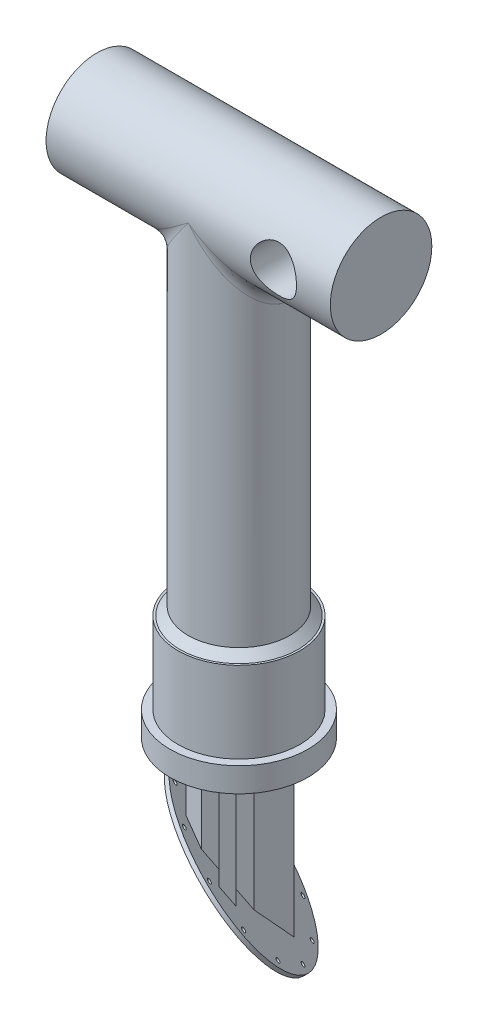
SolidWorks part; units mm, degrees
note: '?' marks a value the reader was unsure of.
ref_plane "前视基准面" through (0, 0, 0) normal (0, 0, 1) x (1, 0, 0)
ref_plane "上视基准面" through (0, 0, 0) normal (0, 1, 0) x (1, 0, 0)
ref_plane "右视基准面" through (0, 0, 0) normal (1, 0, 0) x (0, 0, -1)
sketch "草图1" plane through (0, 0, 0) normal (0, 1, 0) x (1, 0, 0)
  line L1 (0, 0) -> (1, 0)
  line L2 (0, 0) -> (0, 1)
  line L3 (0, 1) -> (1, 1)
  line L4 (1, 0) -> (1, 1)
  dimension "D1" = 1
  dimension "D2" = 1
ref_plane "基准面1" through (0, 1, 0) normal (0, 1, 0) x (1, 0, 0)
sketch "草图2" plane through (0, 1, 0) normal (0, 1, 0) x (1, 0, 0)
  line L1 (0, 0) -> (1, 0)
  line L2 (0, 0) -> (0, 1)
  line L3 (0, 1) -> (1, 1)
  line L4 (1, 0) -> (1, 1)
ref_axis "基准轴1" through (0, 0, 0) along (0.5774, 0.5774, -0.5774)?
ref_plane "基准面2" through (0, 0, 0) normal (0.5774, 0.5774, -0.5774) x (-0.8165, 0.4082, -0.4082)
sketch "草图3" plane through (0, 0, 0) normal (0.5774, 0.5774, -0.5774) x (-0.8165, 0.4082, -0.4082)
  circle A0 centre (0, 0) radius 112.5
  dimension "D1" = 225
extrude "凸台-拉伸1" add sketch "草图3" along normal blind 5 contours A0
sketch "草图5" plane through (0, 1, 0) normal (0, 1, 0) x (1, 0, 0)
  line L1 (0, 0) -> (-50, 0)
  line L2 (0, 0) -> (0, -50)
  line L3 (0, -50) -> (-50, -50)
  line L4 (-50, 0) -> (-50, -50)
  dimension "D1" = 50
  dimension "D2" = 50
ref_axis "基准轴2" through (-50, 1, 50) along (0, 1, 0)?
sketch "草图6" plane through (2.8868, 2.8868, -2.8868) normal (0.5774, 0.5774, -0.5774) x (-0.4082, -0.4082, -0.8165)
  line L0 (0, 0) -> (-51.6754, 89.5044) construction
  line L2 (-20.8207, 36.0624) -> (-102.3071, 177.201) construction
  circle A0 centre (-51.6754, 89.5044) radius 3
  dimension "D1" = 6
extrude "切除-拉伸1" cut sketch "草图6" against normal blind 5
pattern_circular "阵列(圆周)1" count 12 over 360 about axis through (0, 0, 0) along (0.5774, 0.5774, -0.5774) of "切除-拉伸1"
ref_plane "基准面3" through (0, 135, 0) normal (0, 1, 0) x (1, 0, 0)
sketch "草图7" [suppressed] plane through (0, 175, 0) normal (0, 1, 0) x (1, 0, 0)
  circle A0 centre (0, 0) radius 112.5
  dimension "D1" = 225
sketch "草图8" plane through (0, 135, 0) normal (0, 1, 0) x (1, 0, 0)
  line L0 (45.9279, 45.9279) -> (-45.9279, -45.9279) construction
  line L1 (-54.6804, -10.2893) -> (-10.2893, -54.6804)
  line L2 (-10.2893, -54.6804) -> (15.6559, -62.0463)
  line L3 (15.6559, -62.0463) -> (26.6929, -51.0092)
  line L4 (48.1974, -29.5048) -> (52.4911, 15.5798)
  line L5 (52.4911, 15.5798) -> (15.5798, 52.4911)
  line L6 (-54.6804, -10.2893) -> (-62.0463, 15.6559)
  line L7 (-62.0463, 15.6559) -> (-51.0092, 26.6929)
  line L8 (-29.5048, 48.1974) -> (15.5798, 52.4911)
  line L9 (26.6929, -51.0092) -> (45.0412, -69.3575)
  line L10 (45.0412, -69.3575) -> (55.2908, -59.1078)
  line L11 (55.2908, -59.1078) -> (36.9426, -40.7596)
  line L12 (36.9426, -40.7596) -> (48.1974, -29.5048)
  line L13 (-69.3575, 45.0412) -> (-59.1078, 55.2908)
  line L14 (-59.1078, 55.2908) -> (-40.7596, 36.9426)
  line L15 (-51.0092, 26.6929) -> (-69.3575, 45.0412)
  line L16 (-40.7596, 36.9426) -> (-29.5048, 48.1974)
  ellipse E0 centre (0, 0) end of major axis (79.5495, -79.5495) minor radius 64.9519 construction
  ellipse E1 centre (0, 0) end of major axis (79.5495, -79.5495) minor radius 64.9519 construction
  point P14 (0, 0)
  point P29 (-32.4849, -32.4849)
  point P32 (34.0355, 34.0355)
extrude "凸台-拉伸2" add sketch "草图8" against normal up to surface (79.9494 mm away) up to face at (42.9582, 47.2008, 81.4988)
sketch "草图9" plane through (0, 135, 0) normal (0, 1, 0) x (1, 0, 0)
  line L0 (79.5495, -79.5495) -> (-79.5495, 79.5495) construction
  line L1 (24.7487, -24.7487) -> (68.3974, 18.9)
  line L2 (-17.6777, 17.6777) -> (27.1019, 62.4572)
  line L3 (17.6777, -17.6777) -> (62.4572, 27.1019)
  line L4 (-24.7487, 24.7487) -> (18.9, 68.3974)
  line L5 (79.5495, -79.5495) -> (38.8511, -38.8511) construction
  line L6 (26.6929, -51.0092) -> (15.6559, -62.0463) construction
  line L7 (15.6559, -62.0463) -> (26.6929, -51.0092) construction
  line L8 (0, 0) -> (48.8147, 48.8147) construction
  line L9 (0, 0) -> (1, 1) construction
  line L10 (-21.2132, 21.2132) -> (25.9384, 68.3648) construction
  line L11 (21.2132, -21.2132) -> (68.3648, 25.9384) construction
  line L12 (21.2132, -21.2132) -> (70.0279, 27.6015) construction
  line L13 (-21.2132, 21.2132) -> (27.6015, 70.0279) construction
  line L14 (82.849, -75.7779) -> (42.3866, -35.3155)
  line L15 (75.7779, -82.849) -> (35.3155, -42.3866)
  line L16 (76.014, -83.085) -> (35.3155, -42.3866) construction
  line L17 (83.085, -76.014) -> (42.3866, -35.3155) construction
  line L18 (24.7487, -24.7487) -> (71.9003, 22.4028) construction
  line L19 (17.6777, -17.6777) -> (64.8292, 29.4739) construction
  line L20 (-24.7487, 24.7487) -> (22.4028, 71.9003) construction
  line L21 (-17.6777, 17.6777) -> (29.4739, 64.8292) construction
  line L22 (-75.7779, 82.849) -> (-35.3155, 42.3866)
  line L23 (-82.849, 75.7779) -> (-42.3866, 35.3155)
  line L24 (-42.3866, 35.3155) -> (-35.3155, 42.3866)
  line L25 (-24.7487, 24.7487) -> (-17.6777, 17.6777)
  line L26 (17.6777, -17.6777) -> (24.7487, -24.7487)
  line L27 (42.3866, -35.3155) -> (35.3155, -42.3866)
  ellipse E0 centre (2.8868, 2.8868) end of major axis (82.4363, -76.6628) minor radius 64.9519 construction
  ellipse E1 centre (0, 0) end of major axis (79.5495, -79.5495) minor radius 64.9519 construction
  ellipse E2 centre (0, 0) end of major axis (79.5495, -79.5495) minor radius 64.9519 (75.7779, -82.849) -> (82.849, -75.7779) ccw
  ellipse E3 centre (0, 0) end of major axis (79.5495, -79.5495) minor radius 64.9519 (68.3974, 18.9) -> (62.4572, 27.1019) ccw
  ellipse E4 centre (0, 0) end of major axis (79.5495, -79.5495) minor radius 64.9519 (27.1019, 62.4572) -> (18.9, 68.3974) ccw
  ellipse E5 centre (0, 0) end of major axis (-79.5495, 79.5495) minor radius 64.9519 (-82.849, 75.7779) -> (-75.7779, 82.849) cw
  point P4 (0, 0)
  dimension "D1" = 30
  dimension "D2" = 30
  dimension "D3" = 5
  dimension "D4" = 5
  dimension "D5" = 5
  dimension "D6" = 5
extrude "凸台-拉伸3" [suppressed] add sketch "草图9" against normal up to surface (255.8989 mm away)
extrude "凸台-拉伸4" [suppressed] add sketch "草图7" along normal blind 5 contours A0
sketch "草图10" [suppressed] plane through (0, 180, 0) normal (0, 1, 0) x (1, 0, 0)
  line L0 (0, 0) -> (-72.2686, -72.2686) construction
  line L1 (0, 0) -> (1, 1) construction
  circle A0 centre (-72.2686, -72.2686) radius 3
  dimension "D1" = 6
extrude "切除-拉伸2" [suppressed] cut sketch "草图10" against normal blind 5 contours A0
ref_axis "基准轴3" through (0, -108.6804, 0) along (0, 1, 0)?
pattern_circular "阵列(圆周)2" [suppressed] count 12 over 360 about axis through (0, -108.6804, 0) along (0, 1, 0)
sketch "草图11" plane through (0, 135, 0) normal (0, 1, 0) x (1, 0, 0)
  circle A0 centre (0, 0) radius 85
  dimension "D1" = 170
extrude "凸台-拉伸5" add sketch "草图11" along normal blind 30
sketch "草图13" plane through (0, 165, 0) normal (0, 1, 0) x (1, 0, 0)
  circle A0 centre (0, 0) radius 75
  dimension "D1" = 150
extrude "凸台-拉伸6" add sketch "草图13" along normal blind 100
sketch "草图14" plane through (0, 265, 0) normal (0, 1, 0) x (1, 0, 0)
  circle A0 centre (0, 0) radius 62.5
  dimension "D1" = 125
extrude "凸台-拉伸7" add sketch "草图14" along normal blind 450 contours A0
sketch "草图15" plane through (0, 0, 0) normal (1, 0, 0) x (0, 0, -1)
  line L0 (62.5, 715) -> (-62.5, 715) construction
  line L1 (62.5, 715) -> (-62.5, 715) construction
  circle A0 centre (0, 715) radius 62.5
extrude "凸台-拉伸8" add sketch "草图15" along normal mid plane 350
fillet "圆角1" radius 20 2 edges at (-62.5, 652.5, 0) (62.5, 652.5, 0)
chamfer "倒角1" distance 10 angle 45 1 edges at (0, 265, 62.5)
sketch "草图16" plane through (0, 0, 0) normal (0, 0, 1) x (1, 0, 0)
  line L0 (175, 715) -> (104.9178, 715) construction
  line L1 (175, 652.5) -> (175, 777.5) construction
  circle A0 centre (104.9178, 715) radius 28.3975
  point P5 (157, 896)
  point P6 (104.9178, 896)
extrude "切除-拉伸3" cut sketch "草图16" along normal blind 1079
equation "\"drive_od\"= 225mm"
equation "\"D1@草图3\"=\"drive_od\""
equation "\"D1@草图7\"=\"drive_od\""
